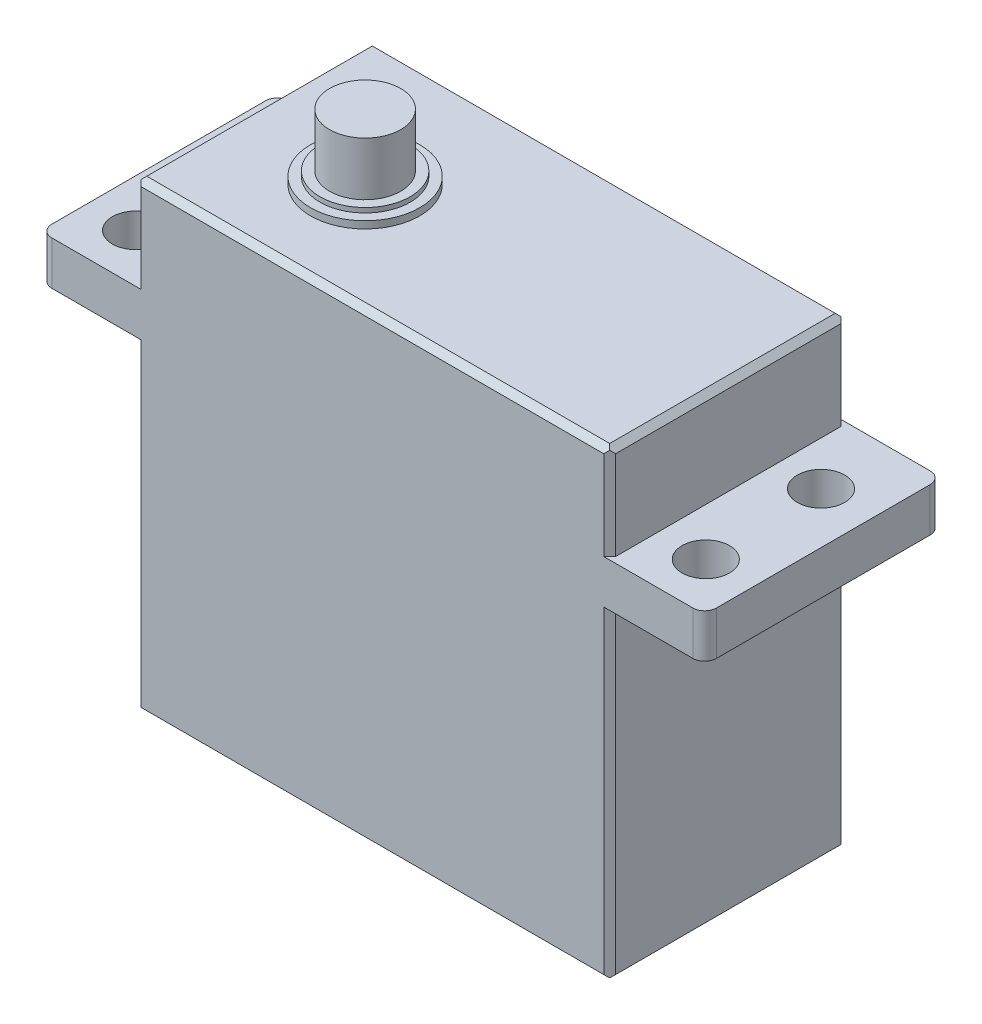
SolidWorks part; units mm, degrees
ref_plane "前视基准面" through (0, 0, 0) normal (0, 0, 1) x (1, 0, 0)
ref_plane "上视基准面" through (0, 0, 0) normal (0, 1, 0) x (1, 0, 0)
ref_plane "右视基准面" through (0, 0, 0) normal (1, 0, 0) x (0, 0, -1)
other "Configuration Table"
sketch "草图1" plane through (0, 0, 0) normal (0, 0, 1) x (1, 0, 0)
  line L1 (-20, -19.5) -> (20, -19.5)
  line L2 (-20, -19.5) -> (-20, 19.5)
  line L3 (-20, 19.5) -> (20, 19.5)
  line L4 (20, -19.5) -> (20, 19.5)
  line L5 (-20, -19.5) -> (20, 19.5) construction
  line L6 (-20, 19.5) -> (20, -19.5) construction
  point P0 (0, 0)
  dimension "D1" = 40
  dimension "D2" = 39
extrude "凸台-拉伸1" add sketch "草图1" along normal blind 20
sketch "草图3" plane through (0, 0, 0) normal (1, 0, 0) x (0, 0, -1)
  line L0 (-20, -19.5) -> (-20, 19.5) construction
  line L1 (-20, 11.5) -> (0, 11.5)
  line L2 (-20, 11.5) -> (-20, 7.8215)
  line L3 (-20, 7.8215) -> (0, 7.8215)
  line L4 (0, 11.5) -> (0, 7.8215)
  line L5 (0, -19.5) -> (0, 19.5) construction
  line L6 (-20, -19.5) -> (0, -19.5) construction
  dimension "D1" = 31
extrude "凸台-拉伸2" add sketch "草图3" along normal blind 28 and the other way blind 28
sketch "草图4" plane through (0, 0, 0) normal (0, 1, 0) x (1, 0, 0)
  line L0 (-20, -5.9023) -> (-23.7031, -5.9023) construction
  line L1 (-20, 0) -> (-20, -20) construction
  line L2 (-20, -15.9023) -> (-24, -15.9023) construction
  line L3 (-20, -20) -> (-20, 0) construction
  circle A0 centre (-23.7031, -5.9023) radius 2
  circle A1 centre (-24, -15.9023) radius 2
  dimension "D4" = 4
  dimension "D5" = 4
  dimension "D1" = 3.7031
  dimension "D2" = 4
  dimension "D3" = 10
extrude "切除-拉伸2" cut sketch "草图4" against normal blind 28 from surface starting at face at (-24, 11.5, 10)
mirror "镜向1" about plane through (0, 0, 0) normal (1, 0, 0) of "切除-拉伸2"
sketch "草图5" plane through (0, 0, 0) normal (0, 1, 0) x (1, 0, 0)
  line L0 (-23.7031, -5.9023) -> (-9.7031, -5.9023) construction
  line L1 (-9.7031, -5.9023) -> (-9.7031, -10.9023) construction
  circle A0 centre (-9.7031, -10.9023) radius 3
  circle A1 centre (-9.7031, -10.9023) radius 3.8
  circle A2 centre (-9.7031, -10.9023) radius 4.6
  dimension "D3" = 6
  dimension "D4" = 7.6
  dimension "D5" = 9.2
  dimension "D1" = 14
  dimension "D2" = 5
extrude "凸台-拉伸5" add sketch "草图5" along normal blind 20.1 separate body contours A2 | A1
sketch "草图7" plane through (0, 0, 0) normal (0, 1, 0) x (1, 0, 0)
  circle A0 centre (-9.7031, -10.9023) radius 3.8
extrude "凸台-拉伸6" add sketch "草图7" along normal blind 20.5
sketch "草图8" plane through (0, 0, 0) normal (0, 1, 0) x (1, 0, 0)
  circle A0 centre (-9.7031, -10.9023) radius 3
  dimension "D1" = 6
extrude "凸台-拉伸7" add sketch "草图8" along normal blind 25
fillet "倒角2" radius 0.5 1 edges at (-20, -19.5, 10) type face fillet profile chamfer first side face at (-20, -5.8392, 10) second side face at (0, -19.5, 10)
fillet "倒角3" radius 0.5 1 edges at (0.25, -19.5, 20) type face fillet profile chamfer first side face at (-1.5, 4.4836, 20) second side face at (0.25, -19.5, 10)
fillet "倒角4" radius 0.5 1 edges at (20, -19.5, 9.75) type face fillet profile chamfer first side face at (20, -8.4714, 11.9) second side face at (0.25, -19.5, 9.75)
fillet "倒角5" radius 0.5 1 edges at (0, -19.5, 0) type face fillet profile chamfer first side face at (0, 2.8062, 0) second side face at (0, -19.5, 9.75)
fillet "倒角6" radius 0.5 1 edges at (-20, -5.5892, 0) type face fillet profile chamfer first side face at (0, 6.5238, 0) second side face at (-20, -5.5892, 10)
fillet "倒角7" radius 0.5 1 edges at (-20, 15.5, 0) type face fillet profile chamfer first side face at (-20, 15.5, 10) second side face at (0.0833, 6.5238, 0)
fillet "倒角8" radius 0.5 1 edges at (20, -5.5892, 0) type face fillet profile chamfer first side face at (20, -5.5892, 10) second side face at (0.1667, 6.5238, 0)
fillet "倒角9" radius 0.5 1 edges at (20, 15.5, 0) type face fillet profile chamfer first side face at (20, 15.5, 10) second side face at (0.0833, 6.5238, 0)
fillet "倒角10" radius 0.5 1 edges at (20, 15.5, 20) type face fillet profile chamfer first side face at (20, 15.5, 10.25) second side face at (0, 6.5238, 20)
fillet "倒角11" radius 0.5 1 edges at (20, -5.5892, 20) type face fillet profile chamfer first side face at (20, -5.5892, 10.25) second side face at (-0.0833, 6.5238, 20)
fillet "倒角12" radius 0.5 1 edges at (-20, 15.5, 20) type face fillet profile chamfer first side face at (-20, 15.5, 10.25) second side face at (-0.1667, 6.5238, 20)
fillet "倒角13" radius 0.5 1 edges at (-20, -5.5892, 20) type face fillet profile chamfer first side face at (-20, -5.5892, 10.25) second side face at (-0.0833, 6.5238, 20)
fillet "倒角14" radius 0.5 1 edges at (0, 19.5, 0) type face fillet profile chamfer first side face at (0, 19.5, 10) second side face at (0, 6.5238, 0)
fillet "倒角15" radius 0.5 1 edges at (20, 19.5, 10) type face fillet profile chamfer first side face at (0, 19.5, 13.3333) second side face at (20, 15.5, 10)
fillet "倒角16" radius 0.5 1 edges at (0, 19.5, 20) type face fillet profile chamfer first side face at (0, 6.5238, 20) second side face at (-4.1, 19.5, 12.1)
fillet "倒角17" radius 0.5 1 edges at (-20, 19.5, 10) type face fillet profile chamfer first side face at (-0.25, 19.5, 10) second side face at (-20, 15.5, 10)
fillet "圆角1" radius 1 1 edges at (-28, 9.6608, 0) type face fillet first side face at (0, 6.4405, 0) second side face at (-28, 9.6608, 10)
fillet "圆角2" radius 1 1 edges at (-28, 9.6608, 20) type face fillet first side face at (-28, 9.6608, 10.5) second side face at (0, 6.4405, 20)
fillet "圆角3" radius 1 1 edges at (28, 9.6608, 20) type face fillet first side face at (28, 9.6608, 10) second side face at (0.1667, 6.4405, 20)
fillet "圆角4" radius 1 1 edges at (28, 9.6608, 0) type face fillet first side face at (28, 9.6608, 9.5) second side face at (0.1667, 6.4405, 0)
